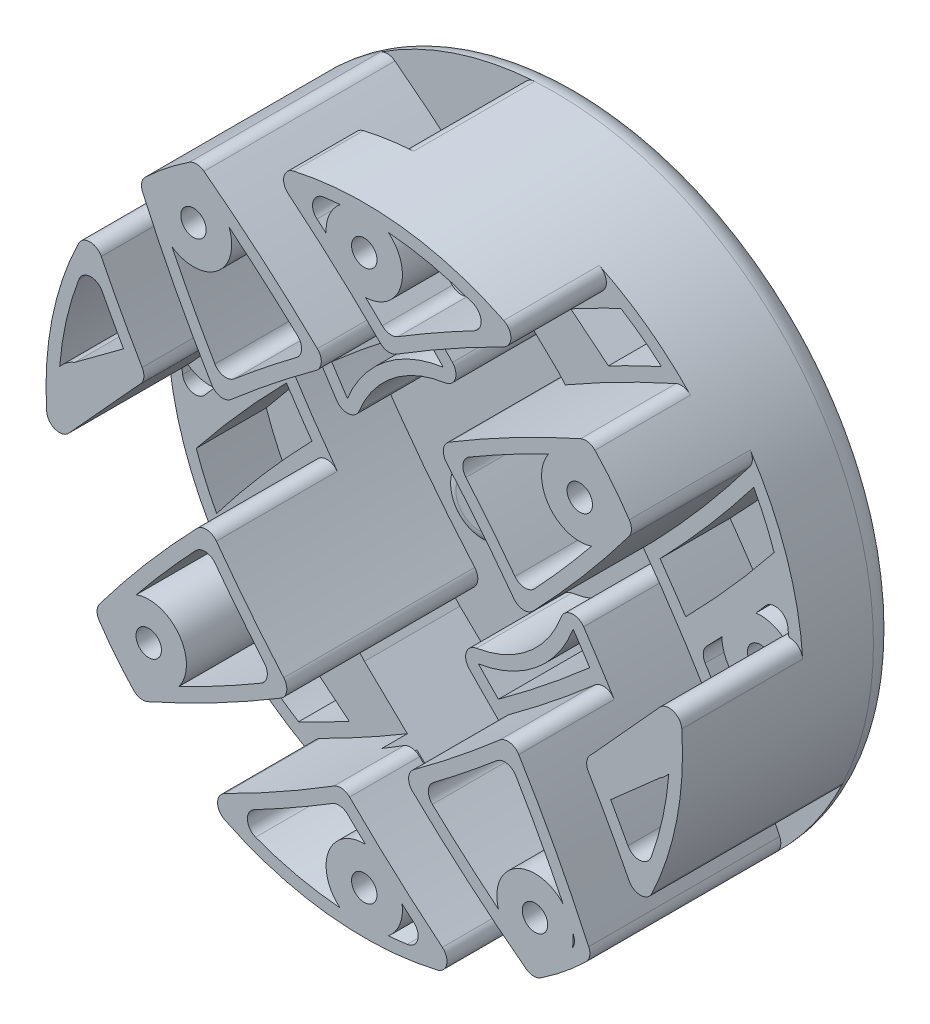
SolidWorks part; units mm, degrees
ref_plane "Front Plane" through (0, 0, 0) normal (0, 0, 1) x (1, 0, 0)
ref_plane "Top Plane" through (0, 0, 0) normal (0, 1, 0) x (1, 0, 0)
ref_plane "Right Plane" through (0, 0, 0) normal (1, 0, 0) x (0, 0, -1)
sketch "Sketch1" plane through (0, 0, 0) normal (0, 0, 1) x (1, 0, 0)
  circle A0 centre (0, 0) radius 25
extrude "Boss-Extrude1" add sketch "Sketch1" along normal blind 2
sketch "Sketch2" plane through (0, 0, 2) normal (0, 0, 1) x (1, 0, 0)
  circle A0 centre (0, 0) radius 2.8
extrude "Boss-Extrude2" add sketch "Sketch2" along normal blind 6
fillet "Fillet1" radius 1 1 edges at (2.8, 0, 8)
sketch "Sketch3" plane through (0, 0, 2) normal (0, 0, 1) x (1, 0, 0)
  line L0 (-25, 0) -> (-25, 25) construction
  line L1 (-25, 25) -> (25, 25) construction
  line L2 (25, 25) -> (25, -25) construction
  line L3 (25, -25) -> (-25, -25) construction
  line L4 (-25, -25) -> (-25, 0) construction
  line L5 (-25, 25) -> (-25, 75) construction
  line L6 (25, 25) -> (75, 25) construction
  line L7 (25, -25) -> (25, -75) construction
  line L8 (-25, -25) -> (-75, -25) construction
  line L9 (-25, 25) -> (25, -25) construction
  line L10 (25, 25) -> (-25, -25) construction
  circle A0 centre (0, 0) radius 25 construction
  circle A5 centre (0, 0) radius 13 construction
sketch "Sketch4" plane through (0, 0, 2) normal (0, 0, 1) x (1, 0, 0)
  line L0 (-25, 25) -> (-25, -9.8016) construction
  line L1 (-25, -25) -> (9.8016, -25) construction
  line L2 (25, -25) -> (25, 9.8016) construction
  line L3 (25, 25) -> (-9.8016, 25) construction
  arc A0 (28.9883, -36.3502) -> (-9.8016, 25) centre (-71.0682, -56.675) ccw construction
  arc A1 (-28.9883, 36.3502) -> (9.8016, -25) centre (71.0682, 56.675) ccw construction
  arc A2 (36.3502, 28.9883) -> (-25, -9.8016) centre (56.675, -71.0682) ccw construction
  arc A3 (-36.3502, -28.9883) -> (25, 9.8016) centre (-56.675, 71.0682) ccw construction
sketch "Sketch5" plane through (0, 0, 2) normal (0, 0, 1) x (1, 0, 0)
  line L0 (-6.2547, -4.9879) -> (0, 0) construction
  arc A0 (-6.4509, -4.7314) -> (-6.0482, -5.2363) centre (0, 0) ccw construction
sketch "Sketch6" plane through (0, 0, 2) normal (0, 0, 1) x (1, 0, 0)
  circle A0 centre (-25, 25) radius 50 construction
  circle A1 centre (25, 25) radius 50 construction
  circle A2 centre (-25, -25) radius 50 construction
  circle A3 centre (25, -25) radius 50 construction
sketch "Sketch7" plane through (0, 0, 2) normal (0, 0, 1) x (1, 0, 0)
  arc A0 (-13.1465, 21.2643) -> (-17.6984, 17.6569) centre (0, 0) ccw
  arc A1 (0.9661, 8.4449) -> (-13.1465, 21.2643) centre (-72.3464, -58.0854) ccw
  arc A3 (0.9661, 8.4449) -> (-8.4219, 1.1498) centre (0, 0) ccw
  arc A4 (-21.5033, 12.7519) -> (7.6467, -23.8018) centre (0, 0) ccw
  arc A8 (21.6702, -12.466) -> (-7.4888, 23.852) centre (-72.3464, -58.0854) ccw
  arc A9 (17.921, -17.4309) -> (8.4542, -0.8816) centre (-72.3464, -58.0854) ccw
  arc A10 (-17.6984, 17.6569) -> (-8.4219, 1.1498) centre (71.0981, 56.6976) ccw
  arc A11 (-21.5033, 12.7519) -> (7.6467, -23.8018) centre (71.0981, 56.6976) ccw
  arc A12 (13.2755, -21.184) -> (17.921, -17.4309) centre (0, 0) ccw
  arc A13 (21.6702, -12.466) -> (-7.4888, 23.852) centre (0, 0) ccw
  arc A14 (-0.7533, -8.4666) -> (8.4542, -0.8816) centre (0, 0) ccw
  arc A15 (-0.7533, -8.4666) -> (13.2755, -21.184) centre (71.0981, 56.6976) ccw
extrude "Boss-Extrude3" add sketch "Sketch7" along normal blind 7.5
sketch "Sketch8" plane through (0, 0, 9.5) normal (0, 0, 1) x (1, 0, 0)
  arc A0 (12.7137, 21.5259) -> (1.8288, 15.5237) centre (56.675, -71.0682) ccw
  arc A7 (17.6291, 17.7261) -> (5.67, 11.4394) centre (56.675, -71.0682) ccw
  arc A8 (-12.3108, -2.8775) -> (-21.2045, -13.2427) centre (56.675, -71.0682) ccw
  arc A9 (12.4368, 3.0052) -> (21.2045, 13.2427) centre (-56.675, 71.0682) ccw
  arc A10 (-17.6291, -17.7261) -> (-5.5449, -11.3619) centre (-56.675, 71.0682) ccw
  arc A11 (-12.7137, -21.5259) -> (-1.7108, -15.4488) centre (-56.675, 71.0682) ccw
  arc A15 (-17.6984, 17.6569) -> (-11.3535, 5.6024) centre (71.0981, 56.6976) ccw
  arc A16 (17.921, -17.4309) -> (11.5101, -5.4632) centre (-72.3464, -58.0854) ccw
  arc A19 (-2.8235, 12.3955) -> (-11.3535, 5.6024) centre (56.675, -71.0682) ccw
  arc A22 (-15.442, 1.77) -> (-23.8152, -7.6049) centre (56.675, -71.0682) ccw
  arc A23 (2.9354, -12.3157) -> (13.2755, -21.184) centre (71.0981, 56.6976) ccw
  arc A25 (2.9354, -12.3157) -> (11.5101, -5.4632) centre (-56.675, 71.0682) ccw
  arc A26 (-2.8235, 12.3955) -> (-13.1465, 21.2643) centre (-72.3464, -58.0854) ccw
  arc A27 (15.5881, -1.625) -> (23.8152, 7.6049) centre (-56.675, 71.0682) ccw
  arc A33 (21.6702, -12.466) -> (15.5881, -1.625) centre (-72.3464, -58.0854) ccw
  arc A35 (-21.5033, 12.7519) -> (-15.442, 1.77) centre (71.0981, 56.6976) ccw
  arc A37 (12.4368, 3.0052) -> (5.67, 11.4394) centre (-72.3464, -58.0854) ccw
  arc A38 (-1.7108, -15.4488) -> (7.6467, -23.8018) centre (71.0981, 56.6976) ccw
  arc A41 (-13.1465, 21.2643) -> (-17.6984, 17.6569) centre (0, 0) ccw
  arc A44 (1.8288, 15.5237) -> (-7.4888, 23.852) centre (-72.3464, -58.0854) ccw
  arc A45 (-12.3108, -2.8775) -> (-5.5449, -11.3619) centre (71.0981, 56.6976) ccw
  arc A48 (12.7137, 21.5259) -> (-7.4888, 23.852) centre (0, 0) ccw
  arc A50 (21.2045, 13.2427) -> (17.6291, 17.7261) centre (0, 0) ccw
  arc A52 (-21.5033, 12.7519) -> (-23.8152, -7.6049) centre (0, 0) ccw
  arc A53 (-21.2045, -13.2427) -> (-17.6291, -17.7261) centre (0, 0) ccw
  arc A54 (-12.7137, -21.5259) -> (7.6467, -23.8018) centre (0, 0) ccw
  arc A55 (13.2755, -21.184) -> (17.921, -17.4309) centre (0, 0) ccw
  arc A56 (21.6702, -12.466) -> (23.8152, 7.6049) centre (0, 0) ccw
extrude "Boss-Extrude5" add sketch "Sketch8" along normal blind 7.5
sketch "Sketch9" plane through (0, 0, 9.5) normal (0, 0, 1) x (1, 0, 0)
  arc A8 (5.8577, 12.7268) -> (3.4142, 15.3352) centre (-72.3464, -58.0854) ccw
  arc A9 (15.8486, 18.0228) -> (5.8577, 12.7268) centre (56.675, -71.0682) ccw
  arc A10 (15.8486, 18.0228) -> (12.6577, 20.3907) centre (0, 0) ccw
  arc A11 (12.6577, 20.3907) -> (3.4142, 15.3352) centre (56.675, -71.0682) ccw
  arc A12 (5.8577, 12.7268) -> (3.4142, 15.3352) centre (-72.3464, -58.0854) ccw
  arc A13 (15.8486, 18.0228) -> (5.8577, 12.7268) centre (56.675, -71.0682) ccw
  arc A14 (15.8486, 18.0228) -> (12.6577, 20.3907) centre (0, 0) ccw
  arc A15 (12.6577, 20.3907) -> (3.4142, 15.3352) centre (56.675, -71.0682) ccw
  arc A17 (10.5207, 21.5711) -> (-5.3354, 23.3994) centre (0, 0) ccw
  arc A18 (1.9721, 16.7945) -> (-5.3354, 23.3994) centre (-72.3464, -58.0854) ccw
  arc A19 (10.5207, 21.5711) -> (1.9721, 16.7945) centre (56.675, -71.0682) ccw
  arc A20 (10.5207, 21.5711) -> (-5.3354, 23.3994) centre (0, 0) ccw
  arc A21 (1.9721, 16.7945) -> (-5.3354, 23.3994) centre (-72.3464, -58.0854) ccw
  arc A22 (10.5207, 21.5711) -> (1.9721, 16.7945) centre (56.675, -71.0682) ccw
  arc A28 (12.5465, 4.552) -> (7.2083, 11.2061) centre (-72.3464, -58.0854) ccw
  arc A29 (12.5465, 4.552) -> (19.9875, 13.2853) centre (-56.675, 71.0682) ccw
  arc A30 (19.9875, 13.2853) -> (17.3998, 16.5302) centre (0, 0) ccw
  arc A31 (17.3998, 16.5302) -> (7.2083, 11.2061) centre (56.675, -71.0682) ccw
  arc A32 (12.5465, 4.552) -> (7.2083, 11.2061) centre (-72.3464, -58.0854) ccw
  arc A33 (12.5465, 4.552) -> (19.9875, 13.2853) centre (-56.675, 71.0682) ccw
  arc A34 (19.9875, 13.2853) -> (17.3998, 16.5302) centre (0, 0) ccw
  arc A35 (17.3998, 16.5302) -> (7.2083, 11.2061) centre (56.675, -71.0682) ccw
  arc A40 (15.7514, -0.0421) -> (13.737, 2.9055) centre (-72.3464, -58.0854) ccw
  arc A41 (15.7514, -0.0421) -> (22.6961, 7.803) centre (-56.675, 71.0682) ccw
  arc A42 (22.6961, 7.803) -> (21.0976, 11.4408) centre (0, 0) ccw
  arc A43 (13.737, 2.9055) -> (21.0976, 11.4408) centre (-56.675, 71.0682) ccw
  arc A44 (15.7514, -0.0421) -> (13.737, 2.9055) centre (-72.3464, -58.0854) ccw
  arc A45 (15.7514, -0.0421) -> (22.6961, 7.803) centre (-56.675, 71.0682) ccw
  arc A46 (22.6961, 7.803) -> (21.0976, 11.4408) centre (0, 0) ccw
  arc A47 (13.737, 2.9055) -> (21.0976, 11.4408) centre (-56.675, 71.0682) ccw
  arc A50 (21.6937, -10.2657) -> (23.3714, 5.4569) centre (0, 0) ccw
  arc A51 (16.8621, -1.7641) -> (23.3714, 5.4569) centre (-56.675, 71.0682) ccw
  arc A52 (21.6937, -10.2657) -> (16.8621, -1.7641) centre (-72.3464, -58.0854) ccw
  arc A53 (21.6937, -10.2657) -> (23.3714, 5.4569) centre (0, 0) ccw
  arc A54 (16.8621, -1.7641) -> (23.3714, 5.4569) centre (-56.675, 71.0682) ccw
  arc A55 (21.6937, -10.2657) -> (16.8621, -1.7641) centre (-72.3464, -58.0854) ccw
  arc A61 (-13.1932, 20.0484) -> (-16.502, 17.4265) centre (0, 0) ccw
  arc A62 (-16.502, 17.4265) -> (-11.1198, 7.1375) centre (71.0981, 56.6976) ccw
  arc A63 (-4.3737, 12.51) -> (-11.1198, 7.1375) centre (56.675, -71.0682) ccw
  arc A64 (-4.3737, 12.51) -> (-13.1932, 20.0484) centre (-72.3464, -58.0854) ccw
  arc A65 (-13.1932, 20.0484) -> (-16.502, 17.4265) centre (0, 0) ccw
  arc A66 (-16.502, 17.4265) -> (-11.1198, 7.1375) centre (71.0981, 56.6976) ccw
  arc A67 (-4.3737, 12.51) -> (-11.1198, 7.1375) centre (56.675, -71.0682) ccw
  arc A68 (-4.3737, 12.51) -> (-13.1932, 20.0484) centre (-72.3464, -58.0854) ccw
  arc A73 (-1.2957, 9.4112) -> (-2.9278, 11.0887) centre (-72.3464, -58.0854) ccw
  arc A74 (-2.9278, 11.0887) -> (-10.0552, 5.4128) centre (56.675, -71.0682) ccw
  arc A75 (-10.0552, 5.4128) -> (-8.8253, 3.5164) centre (71.0981, 56.6976) ccw
  arc A76 (-1.2957, 9.4112) -> (-8.8253, 3.5164) centre (0, 0) ccw
  arc A77 (-1.2957, 9.4112) -> (-2.9278, 11.0887) centre (-72.3464, -58.0854) ccw
  arc A78 (-2.9278, 11.0887) -> (-10.0552, 5.4128) centre (56.675, -71.0682) ccw
  arc A79 (-10.0552, 5.4128) -> (-8.8253, 3.5164) centre (71.0981, 56.6976) ccw
  arc A80 (-1.2957, 9.4112) -> (-8.8253, 3.5164) centre (0, 0) ccw
  arc A85 (1.4642, -9.3865) -> (3.0394, -11.0077) centre (71.0981, 56.6976) ccw
  arc A86 (3.0394, -11.0077) -> (10.2091, -5.2783) centre (-56.675, 71.0682) ccw
  arc A87 (10.2091, -5.2783) -> (8.9089, -3.2987) centre (-72.3464, -58.0854) ccw
  arc A88 (1.4642, -9.3865) -> (8.9089, -3.2987) centre (0, 0) ccw
  arc A89 (1.4642, -9.3865) -> (3.0394, -11.0077) centre (71.0981, 56.6976) ccw
  arc A90 (3.0394, -11.0077) -> (10.2091, -5.2783) centre (-56.675, 71.0682) ccw
  arc A91 (10.2091, -5.2783) -> (8.9089, -3.2987) centre (-72.3464, -58.0854) ccw
  arc A92 (1.4642, -9.3865) -> (8.9089, -3.2987) centre (0, 0) ccw
  arc A97 (13.3172, -19.9663) -> (16.7238, -17.2137) centre (0, 0) ccw
  arc A98 (16.7238, -17.2137) -> (11.2829, -6.9958) centre (-72.3464, -58.0854) ccw
  arc A99 (4.4839, -12.4294) -> (11.2829, -6.9958) centre (-56.675, 71.0682) ccw
  arc A100 (4.4839, -12.4294) -> (13.3172, -19.9663) centre (71.0981, 56.6976) ccw
  arc A101 (13.3172, -19.9663) -> (16.7238, -17.2137) centre (0, 0) ccw
  arc A102 (16.7238, -17.2137) -> (11.2829, -6.9958) centre (-72.3464, -58.0854) ccw
  arc A103 (4.4839, -12.4294) -> (11.2829, -6.9958) centre (-56.675, 71.0682) ccw
  arc A104 (4.4839, -12.4294) -> (13.3172, -19.9663) centre (71.0981, 56.6976) ccw
  arc A107 (-21.5507, 10.5626) -> (-23.3714, -5.4569) centre (0, 0) ccw
  arc A108 (-16.7139, 1.9135) -> (-23.3714, -5.4569) centre (56.675, -71.0682) ccw
  arc A109 (-21.5507, 10.5626) -> (-16.7139, 1.9135) centre (71.0981, 56.6976) ccw
  arc A110 (-21.5507, 10.5626) -> (-23.3714, -5.4569) centre (0, 0) ccw
  arc A111 (-16.7139, 1.9135) -> (-23.3714, -5.4569) centre (56.675, -71.0682) ccw
  arc A112 (-21.5507, 10.5626) -> (-16.7139, 1.9135) centre (71.0981, 56.6976) ccw
  arc A118 (-22.6961, -7.803) -> (-21.0976, -11.4408) centre (0, 0) ccw
  arc A119 (-13.6095, -2.774) -> (-21.0976, -11.4408) centre (56.675, -71.0682) ccw
  arc A120 (-15.6113, 0.1846) -> (-13.6095, -2.774) centre (71.0981, 56.6976) ccw
  arc A121 (-15.6113, 0.1846) -> (-22.6961, -7.803) centre (56.675, -71.0682) ccw
  arc A122 (-22.6961, -7.803) -> (-21.0976, -11.4408) centre (0, 0) ccw
  arc A123 (-13.6095, -2.774) -> (-21.0976, -11.4408) centre (56.675, -71.0682) ccw
  arc A124 (-15.6113, 0.1846) -> (-13.6095, -2.774) centre (71.0981, 56.6976) ccw
  arc A125 (-15.6113, 0.1846) -> (-22.6961, -7.803) centre (56.675, -71.0682) ccw
  arc A130 (-19.9875, -13.2853) -> (-17.3998, -16.5302) centre (0, 0) ccw
  arc A131 (-17.3998, -16.5302) -> (-7.08, -11.1288) centre (-56.675, 71.0682) ccw
  arc A132 (-12.4252, -4.4261) -> (-7.08, -11.1288) centre (71.0981, 56.6976) ccw
  arc A133 (-12.4252, -4.4261) -> (-19.9875, -13.2853) centre (56.675, -71.0682) ccw
  arc A134 (-19.9875, -13.2853) -> (-17.3998, -16.5302) centre (0, 0) ccw
  arc A135 (-17.3998, -16.5302) -> (-7.08, -11.1288) centre (-56.675, 71.0682) ccw
  arc A136 (-12.4252, -4.4261) -> (-7.08, -11.1288) centre (71.0981, 56.6976) ccw
  arc A137 (-12.4252, -4.4261) -> (-19.9875, -13.2853) centre (56.675, -71.0682) ccw
  arc A142 (-15.8486, -18.0228) -> (-12.6577, -20.3907) centre (0, 0) ccw
  arc A143 (-12.6577, -20.3907) -> (-3.2941, -15.261) centre (-56.675, 71.0682) ccw
  arc A144 (-5.7329, -12.6511) -> (-3.2941, -15.261) centre (71.0981, 56.6976) ccw
  arc A145 (-15.8486, -18.0228) -> (-5.7329, -12.6511) centre (-56.675, 71.0682) ccw
  arc A146 (-15.8486, -18.0228) -> (-12.6577, -20.3907) centre (0, 0) ccw
  arc A147 (-12.6577, -20.3907) -> (-3.2941, -15.261) centre (-56.675, 71.0682) ccw
  arc A148 (-5.7329, -12.6511) -> (-3.2941, -15.261) centre (71.0981, 56.6976) ccw
  arc A149 (-15.8486, -18.0228) -> (-5.7329, -12.6511) centre (-56.675, 71.0682) ccw
  arc A152 (-10.5207, -21.5711) -> (5.5018, -23.3609) centre (0, 0) ccw
  arc A153 (-1.8538, -16.7208) -> (5.5018, -23.3609) centre (71.0981, 56.6976) ccw
  arc A154 (-10.5207, -21.5711) -> (-1.8538, -16.7208) centre (-56.675, 71.0682) ccw
  arc A155 (-10.5207, -21.5711) -> (5.5018, -23.3609) centre (0, 0) ccw
  arc A156 (-1.8538, -16.7208) -> (5.5018, -23.3609) centre (71.0981, 56.6976) ccw
  arc A157 (-10.5207, -21.5711) -> (-1.8538, -16.7208) centre (-56.675, 71.0682) ccw
  dimension "D1" = 1
  dimension "D2" = 1
  dimension "D3" = 1
  dimension "D4" = 1
  dimension "D5" = 1
  dimension "D6" = 1
  dimension "D7" = 1
  dimension "D8" = 1
  dimension "D9" = 1
  dimension "D10" = 1
  dimension "D11" = 1
  dimension "D12" = 1
  dimension "D13" = 1
  dimension "D14" = 1
extrude "Cut-Extrude1" cut sketch "Sketch9" against normal blind 7.5 and the other way blind 7.5
fillet "Fillet2" radius 1 60 edges at (5.5018, -23.3609, 9.5) (-1.8538, -16.7208, 9.5) (-10.5207, -21.5711, 9.5) (7.6467, -23.8018, 9.5) (-12.7137, -21.5259, 13.25) (-1.7108, -15.4488, 13.25) (-17.3998, -16.5302, 9.5) (-19.9875, -13.2853, 9.5) (-12.4252, -4.4261, 9.5) (-7.08, -11.1288, 9.5) (-5.5449, -11.3619, 13.25) (-17.6291, -17.7261, 13.25) (-21.2045, -13.2427, 13.25) (-12.3108, -2.8775, 13.25) (-15.442, 1.77, 13.25) (-21.5507, 10.5626, 9.5) (-16.7139, 1.9135, 9.5) (-23.3714, -5.4569, 9.5) (-23.8152, -7.6049, 13.25) (-21.5033, 12.7519, 9.5) (-16.502, 17.4265, 9.5) (-13.1932, 20.0484, 9.5) (-17.6984, 17.6569, 9.5) (-13.1465, 21.2643, 9.5) (-11.1198, 7.1375, 9.5) (-4.3737, 12.51, 9.5) (-2.8235, 12.3955, 13.25) (-11.3535, 5.6024, 13.25) (-8.4219, 1.1498, 5.75) (0.9661, 8.4449, 5.75) (11.2829, -6.9958, 9.5) (4.4839, -12.4294, 9.5) (2.9354, -12.3157, 13.25) (11.5101, -5.4632, 13.25) (8.4542, -0.8816, 5.75) (-0.7533, -8.4666, 5.75) (13.2755, -21.184, 9.5) (13.3172, -19.9663, 9.5) (16.7238, -17.2137, 9.5) (17.921, -17.4309, 9.5) (21.6702, -12.466, 9.5) (23.8152, 7.6049, 13.25) (15.5881, -1.625, 13.25) (21.6937, -10.2657, 9.5) (23.3714, 5.4569, 9.5) (16.8621, -1.7641, 9.5) (12.4368, 3.0052, 13.25) (5.67, 11.4394, 13.25) (1.8288, 15.5237, 13.25) (21.2045, 13.2427, 13.25) (19.9875, 13.2853, 9.5) (12.5465, 4.552, 9.5) (7.2083, 11.2061, 9.5) (17.3998, 16.5302, 9.5) (17.6291, 17.7261, 13.25) (12.7137, 21.5259, 13.25) (-7.4888, 23.852, 9.5) (1.9721, 16.7945, 9.5) (10.5207, 21.5711, 9.5) (-5.3354, 23.3994, 9.5)
sketch "Sketch10" plane through (0, 0, 2) normal (0, 0, 1) x (1, 0, 0)
  line L0 (0, 0) -> (0, 50000) construction
  line L1 (0, 0) -> (50000, 0) construction
  circle A0 centre (0, 21.6011) radius 1
  circle A1 centre (0, 21.6011) radius 3
extrude "Boss-Extrude6" add sketch "Sketch10" along normal up to surface (15 mm away) up to face at (2.3897, 20.6154, 17)
pattern_circular "CirPattern1" count 4 over 360 about axis through (0, 0, 8) along (0, 0, -1) of "Boss-Extrude6"
sketch "Sketch11" plane through (0, 0, 17) normal (0, 0, 1) x (1, 0, 0)
  line L0 (0, 0) -> (50000, 0) construction
  line L1 (25, 25) -> (-25, -25) construction
  line L2 (0, 0) -> (0, 50000) construction
  point P4 (0, 0)
fillet "Fillet3" radius 2 1 edges at (25, 0, 0)
sketch "Sketch12" plane through (0, 0, 8) normal (0, 0, 1) x (1, 0, 0)
  line L0 (-14.9041, 18.8114) -> (0, 0) construction
  line L1 (0, 0) -> (39190.421, 31050.1354) construction
  circle A0 centre (0, 0) radius 21.6011 construction
  circle A1 centre (13.4143, -16.9311) radius 1
  circle A2 centre (-13.4143, 16.9311) radius 1
  circle A3 centre (-13.4143, 16.9311) radius 3
  circle A4 centre (16.9311, 13.4143) radius 1
  circle A5 centre (16.9311, 13.4143) radius 3
  circle A6 centre (-16.9311, -13.4143) radius 1
  circle A7 centre (-16.9311, -13.4143) radius 2.962
  circle A8 centre (13.4143, -16.9311) radius 3
extrude "Boss-Extrude7" add sketch "Sketch12" along normal up to surface (9 mm away) and the other way up to surface (6 mm away) up to face at (-11.3595, 14.3592, 17) other way up to face at (2.8, 0, 2)
sketch "Sketch13" plane through (0, 0, 9.5) normal (0, 0, 1) x (1, 0, 0)
  line L2 (-4.0651, 24.9442) -> (-8.3875, 24.9442)
  line L3 (-8.3875, 24.9442) -> (-6.5634, 22.5082)
  line L4 (-6.5634, 22.5082) -> (-5.9706, 22.6271)
  line L5 (6.1355, -22.5874) -> (11.1398, -23.8425)
  line L6 (11.1398, -23.8425) -> (4.2342, -24.9079)
  arc A9 (3.381, 18.2141) -> (-4.0651, 24.9442) centre (-72.3464, -58.0854) ccw
  arc A10 (1.2677, 16.0848) -> (-5.9706, 22.6271) centre (-72.3464, -58.0854) ccw
  arc A11 (1.2677, 16.0848) -> (-5.9706, 22.6271) centre (-72.3464, -58.0854) ccw
  arc A12 (8.2921, 13.0038) -> (3.381, 18.2141) centre (-72.3464, -58.0854) ccw
  arc A14 (8.7164, 12.5196) -> (3.381, 18.2141) centre (-72.3464, -58.0854) ccw construction
  arc A15 (16.9907, 17.4426) -> (6.693, 12.0631) centre (56.675, -71.0682) ccw
  arc A16 (6.4542, 10.5493) -> (1.2677, 16.0848) centre (-72.3464, -58.0854) ccw
  arc A17 (6.693, 12.0631) -> (6.4542, 10.5493) centre (7.2083, 11.2061) ccw
  arc A18 (16.9907, 17.4426) -> (6.693, 12.0631) centre (56.675, -71.0682) ccw
  arc A19 (18.1248, 17.2189) -> (16.9907, 17.4426) centre (17.3998, 16.5302) ccw
  arc A20 (18.1248, 17.2189) -> (10.9591, 22.4699) centre (0, 0) ccw
  arc A21 (10.9667, 20.6761) -> (10.9591, 22.4699) centre (10.5207, 21.5711) ccw
  arc A22 (10.9667, 20.6761) -> (2.5007, 15.9456) centre (56.675, -71.0682) ccw
  arc A23 (1.2677, 16.0848) -> (2.5007, 15.9456) centre (1.9721, 16.7945) ccw
  arc A24 (6.4542, 10.5493) -> (1.2677, 16.0848) centre (-72.3464, -58.0854) ccw
  arc A25 (6.693, 12.0631) -> (6.4542, 10.5493) centre (7.2083, 11.2061) ccw
  arc A32 (-18.1248, -17.2189) -> (-10.9591, -22.4699) centre (0, 0) ccw
  arc A33 (-10.9667, -20.6761) -> (-10.9591, -22.4699) centre (-10.5207, -21.5711) ccw
  arc A34 (-10.9667, -20.6761) -> (-2.3835, -15.8726) centre (-56.675, 71.0682) ccw
  arc A35 (-1.149, -16.0114) -> (-2.3835, -15.8726) centre (-1.8538, -16.7208) ccw
  arc A36 (-6.3247, -10.4735) -> (-1.149, -16.0114) centre (71.0981, 56.6976) ccw
  arc A37 (-6.5634, -11.985) -> (-6.3247, -10.4735) centre (-7.08, -11.1288) ccw
  arc A38 (-16.9907, -17.4426) -> (-6.5634, -11.985) centre (-56.675, 71.0682) ccw
  arc A39 (-18.1248, -17.2189) -> (-16.9907, -17.4426) centre (-17.3998, -16.5302) ccw
  arc A44 (-6.3247, -10.4735) -> (-1.149, -16.0114) centre (71.0981, 56.6976) ccw
  arc A45 (-6.5634, -11.985) -> (-6.3247, -10.4735) centre (-7.08, -11.1288) ccw
  arc A48 (8.2921, 13.0038) -> (6.693, 12.0631) centre (56.675, -71.0682) ccw
  arc A50 (-8.163, -12.9294) -> (-3.2635, -18.1395) centre (71.0981, 56.6976) ccw
  arc A51 (-1.149, -16.0114) -> (6.1355, -22.5874) centre (71.0981, 56.6976) ccw
  arc A52 (-1.149, -16.0114) -> (6.1355, -22.5874) centre (71.0981, 56.6976) ccw
  arc A53 (-3.2635, -18.1395) -> (4.2342, -24.9079) centre (71.0981, 56.6976) ccw
  arc A55 (-8.5907, -12.4395) -> (-3.2635, -18.1395) centre (71.0981, 56.6976) ccw construction
  arc A56 (-16.9907, -17.4426) -> (-6.5634, -11.985) centre (-56.675, 71.0682) ccw
  arc A57 (-8.163, -12.9294) -> (-6.5634, -11.985) centre (-56.675, 71.0682) ccw
  dimension "D1" = 0
  dimension "D2" = 0
  dimension "D3" = 0
  dimension "D4" = 3
  dimension "D5" = 0
  dimension "D6" = 0
  dimension "D7" = 3
  dimension "D8" = 0
extrude "Cut-Extrude2" cut sketch "Sketch13" against normal up to surface (7.5 mm away) up to face at (2.8, 0, 2)
sketch "Sketch15" plane through (0, 0, 17) normal (0, 0, 1) x (1, 0, 0)
  line L0 (-18.132, 3.3238) -> (-17.0584, 4.4035)
  line L1 (18.2832, -3.1715) -> (17.2176, -4.2474)
  line L2 (24.3452, 5.6843) -> (24.9182, 4.1891)
  line L3 (-24.9182, -4.1891) -> (-24.3452, -5.6843)
  arc A8 (-20.6555, 11.0083) -> (-15.8655, 2.4428) centre (71.0981, 56.6976) ccw
  arc A9 (-24.3452, -5.6843) -> (-22.598, -6.0909) centre (-23.3714, -5.4569) ccw
  arc A10 (-16.0048, 1.2084) -> (-15.8655, 2.4428) centre (-16.7139, 1.9135) ccw
  arc A11 (-16.0048, 1.2084) -> (-22.598, -6.0909) centre (56.675, -71.0682) ccw
  arc A12 (-24.3452, -5.6843) -> (-22.598, -6.0909) centre (-23.3714, -5.4569) ccw
  arc A13 (-16.0048, 1.2084) -> (-15.8655, 2.4428) centre (-16.7139, 1.9135) ccw
  arc A14 (-16.0048, 1.2084) -> (-22.598, -6.0909) centre (56.675, -71.0682) ccw
  arc A15 (-17.0584, 4.4035) -> (-15.8655, 2.4428) centre (71.0981, 56.6976) ccw
  arc A25 (-18.132, 3.3238) -> (-24.9182, -4.1891) centre (56.675, -71.0682) ccw
  arc A26 (18.2832, -3.1715) -> (24.9182, 4.1891) centre (-56.675, 71.0682) ccw
  arc A29 (24.3452, 5.6843) -> (22.598, 6.0909) centre (23.3714, 5.4569) ccw
  arc A30 (16.1516, -1.0604) -> (22.598, 6.0909) centre (-56.675, 71.0682) ccw
  arc A31 (16.1516, -1.0604) -> (16.0166, -2.298) centre (16.8621, -1.7641) ccw
  arc A32 (20.8023, -10.719) -> (16.0166, -2.298) centre (-72.3464, -58.0854) ccw
  arc A33 (24.3452, 5.6843) -> (22.598, 6.0909) centre (23.3714, 5.4569) ccw
  arc A34 (16.1516, -1.0604) -> (22.598, 6.0909) centre (-56.675, 71.0682) ccw
  arc A35 (16.1516, -1.0604) -> (16.0166, -2.298) centre (16.8621, -1.7641) ccw
  arc A36 (17.2176, -4.2474) -> (16.0166, -2.298) centre (-72.3464, -58.0854) ccw
  dimension "D1" = 0
  dimension "D2" = 0
  dimension "D3" = 0
  dimension "D4" = 3
extrude "Cut-Extrude3" cut sketch "Sketch15" against normal up to surface (7.5 mm away) up to face at (-18.2376, -5.3028, 9.5)
sketch "Sketch16" plane through (0, 0, 17) normal (0, 0, 1) x (1, 0, 0)
  line L0 (-17.0584, 4.4035) -> (-17.7864, 3.6714)
  line L1 (-17.7864, 3.6714) -> (-24.6917, -3.9138)
  line L2 (24.6917, 3.9138) -> (17.9435, -3.5145)
  line L3 (17.9435, -3.5145) -> (17.2176, -4.2474)
  line L4 (-24.6917, -3.9138) -> (-23.9249, 1.8973)
  line L5 (-23.9249, 1.8973) -> (-18.9114, 5.6042)
  line L6 (-18.9114, 5.6042) -> (-17.0584, 4.4035)
  line L7 (24.6917, 3.9138) -> (23.9249, -1.8973)
  line L8 (23.9249, -1.8973) -> (19.3608, -5.9314)
  line L9 (19.3608, -5.9314) -> (17.2176, -4.2474)
  arc A0 (-20.5934, 8.6882) -> (-17.1256, 2.5791) centre (71.0981, 56.6976) ccw construction
  arc A1 (20.7135, -8.3852) -> (17.9435, -3.5145) centre (-72.3464, -58.0854) ccw construction
extrude "Boss-Extrude8" add sketch "Sketch16" against normal up to surface (15 mm away) up to face at (19.9796, -4.1029, 2)
sketch "Sketch17" plane through (0, 0, 2) normal (0, 0, 1) x (1, 0, 0)
  line L0 (-3.7837, 24.712) -> (7.7243, 13.6428)
  line L1 (7.7243, 13.6428) -> (8.2921, 13.0038)
  line L2 (3.9619, -24.6841) -> (-7.4858, -13.6928)
  line L3 (-7.4858, -13.6928) -> (-8.163, -12.9294)
  line L4 (-3.7837, 24.712) -> (1.8973, 23.9249)
  line L5 (1.8973, 23.9249) -> (11.6805, 15.9922)
  line L6 (11.6805, 15.9922) -> (8.2921, 13.0038)
  line L7 (3.9619, -24.6841) -> (-1.8973, -23.9249)
  line L8 (-1.8973, -23.9249) -> (-11.6151, -15.9583)
  line L9 (-11.6151, -15.9583) -> (-8.163, -12.9294)
  arc A0 (8.2921, 13.0038) -> (7.6132, 13.7666) centre (-72.3464, -58.0854) ccw construction
  arc A1 (15.8486, 18.0228) -> (7.6132, 13.7666) centre (56.675, -71.0682) ccw construction
  arc A2 (-15.8486, -18.0228) -> (-7.4858, -13.6928) centre (-56.675, 71.0682) ccw construction
extrude "Boss-Extrude9" add sketch "Sketch17" along normal up to surface (7.5 mm away) up to face at (-11.1272, -17.7153, 9.5)
fillet "Fillet4" radius 1 6 edges at (3.9619, -24.6841, 5.75) (-3.7837, 24.712, 5.75) (-17.0584, 4.4035, 13.25) (-24.6917, -3.9138, 13.25) (17.2176, -4.2474, 13.25) (24.6917, 3.9138, 13.25)
sketch "Sketch18" plane through (0, 0, 9.5) normal (0, 0, -1) x (-1, 0, 0)
  line L6 (-3.4862, 17.7193) -> (-4.2333, 17.0007)
  line L7 (2.2422, 23.2292) -> (0.9304, 21.9675)
  line L8 (-0.4023, 20.6856) -> (-1.8806, 19.2637)
  line L9 (-3.4862, 17.7193) -> (-4.2333, 17.0007)
  line L10 (2.2422, 23.2292) -> (0.9304, 21.9675)
  line L11 (-0.4023, 20.6856) -> (-1.8806, 19.2637)
  arc A32 (-2.5007, 15.9456) -> (-4.2333, 17.0007) centre (-56.675, -71.0682) ccw
  arc A33 (-2.5007, 15.9456) -> (-1.2677, 16.0848) centre (-1.9721, 16.7945) ccw
  arc A34 (5.9706, 22.6271) -> (-1.2677, 16.0848) centre (72.3464, -58.0854) ccw
  arc A35 (5.9706, 22.6271) -> (5.5577, 24.3744) centre (5.3354, 23.3994) ccw
  arc A36 (5.5577, 24.3744) -> (1.6135, 24.9479) centre (0, 0) ccw
  arc A37 (2.5453, 23.8646) -> (1.6135, 24.9479) centre (1.549, 23.95) ccw
  arc A38 (3.1936, 23.7866) -> (2.5453, 23.8646) centre (0, 0) ccw
  arc A39 (3.7111, 22.036) -> (3.1936, 23.7866) centre (3.0605, 22.7955) ccw
  arc A40 (3.7111, 22.036) -> (2.9943, 21.4164) centre (72.3464, -58.0854) ccw
  arc A41 (2.9943, 21.4164) -> (2.3919, 23.4119) centre (0, 21.6011) ccw
  arc A42 (2.2422, 23.2292) -> (2.3919, 23.4119) centre (1.549, 23.95) ccw
  arc A43 (-0.4023, 20.6856) -> (0.9304, 21.9675) centre (0, 21.6011) ccw
  arc A44 (-1.8806, 19.2637) -> (-0.1047, 18.6029) centre (0, 21.6011) ccw
  arc A45 (-0.1047, 18.6029) -> (-1.4156, 17.3428) centre (72.3464, -58.0854) ccw
  arc A46 (-2.6369, 17.2049) -> (-1.4156, 17.3428) centre (-2.1148, 18.0578) ccw
  arc A47 (-2.6369, 17.2049) -> (-3.4862, 17.7193) centre (-56.675, -71.0682) ccw
  arc A48 (-2.5007, 15.9456) -> (-4.2333, 17.0007) centre (-56.675, -71.0682) ccw
  arc A49 (-2.5007, 15.9456) -> (-1.2677, 16.0848) centre (-1.9721, 16.7945) ccw
  arc A50 (5.9706, 22.6271) -> (-1.2677, 16.0848) centre (72.3464, -58.0854) ccw
  arc A51 (5.9706, 22.6271) -> (5.5577, 24.3744) centre (5.3354, 23.3994) ccw
  arc A52 (5.5577, 24.3744) -> (1.6135, 24.9479) centre (0, 0) ccw
  arc A53 (2.5453, 23.8646) -> (1.6135, 24.9479) centre (1.549, 23.95) ccw
  arc A54 (3.1936, 23.7866) -> (2.5453, 23.8646) centre (0, 0) ccw
  arc A55 (3.7111, 22.036) -> (3.1936, 23.7866) centre (3.0605, 22.7955) ccw
  arc A56 (3.7111, 22.036) -> (2.9943, 21.4164) centre (72.3464, -58.0854) ccw
  arc A57 (2.9943, 21.4164) -> (2.3919, 23.4119) centre (0, 21.6011) ccw
  arc A58 (2.2422, 23.2292) -> (2.3919, 23.4119) centre (1.549, 23.95) ccw
  arc A59 (-0.4023, 20.6856) -> (0.9304, 21.9675) centre (0, 21.6011) ccw
  arc A60 (-1.8806, 19.2637) -> (-0.1047, 18.6029) centre (0, 21.6011) ccw
  arc A61 (-0.1047, 18.6029) -> (-1.4156, 17.3428) centre (72.3464, -58.0854) ccw
  arc A62 (-2.6369, 17.2049) -> (-1.4156, 17.3428) centre (-2.1148, 18.0578) ccw
  arc A63 (-2.6369, 17.2049) -> (-3.4862, 17.7193) centre (-56.675, -71.0682) ccw
  dimension "D1" = 0
extrude "Cut-Extrude4" cut sketch "Sketch18" against normal blind 2
sketch "Sketch19" plane through (0, 0, 9.5) normal (0, 0, -1) x (-1, 0, 0)
  line L6 (3.3668, -17.6476) -> (4.1144, -16.9298)
  line L7 (-2.4324, -23.2155) -> (-0.9763, -21.8175)
  line L8 (0.2559, -20.6344) -> (1.7711, -19.1796)
  line L9 (3.3668, -17.6476) -> (4.1144, -16.9298)
  line L10 (-2.4324, -23.2155) -> (-0.9763, -21.8175)
  line L11 (0.2559, -20.6344) -> (1.7711, -19.1796)
  arc A32 (2.3835, -15.8726) -> (4.1144, -16.9298) centre (56.675, 71.0682) ccw
  arc A33 (2.3835, -15.8726) -> (1.149, -16.0114) centre (1.8538, -16.7208) ccw
  arc A34 (-6.1355, -22.5874) -> (1.149, -16.0114) centre (-71.0981, 56.6976) ccw
  arc A35 (-6.1355, -22.5874) -> (-5.731, -24.3342) centre (-5.5018, -23.3609) ccw
  arc A36 (-5.731, -24.3342) -> (-1.8123, -24.9342) centre (0, 0) ccw
  arc A37 (-2.7355, -23.8436) -> (-1.8123, -24.9342) centre (-1.7398, -23.9369) ccw
  arc A38 (-3.3788, -23.761) -> (-2.7355, -23.8436) centre (0, 0) ccw
  arc A39 (-3.8874, -22.0105) -> (-3.3788, -23.761) centre (-3.238, -22.7709) ccw
  arc A40 (-3.8874, -22.0105) -> (-2.9761, -21.2231) centre (-71.0981, 56.6976) ccw
  arc A41 (-2.9761, -21.2231) -> (-2.4895, -23.2751) centre (0, -21.6011) ccw
  arc A42 (-2.4324, -23.2155) -> (-2.4895, -23.2751) centre (-1.7398, -23.9369) ccw
  arc A43 (0.2559, -20.6344) -> (-0.9763, -21.8175) centre (0, -21.6011) ccw
  arc A44 (1.7711, -19.1796) -> (-0.09, -18.6024) centre (0, -21.6011) ccw
  arc A45 (-0.09, -18.6024) -> (1.2965, -17.2703) centre (-71.0981, 56.6976) ccw
  arc A46 (2.5193, -17.1328) -> (1.2965, -17.2703) centre (1.996, -17.985) ccw
  arc A47 (2.5193, -17.1328) -> (3.3668, -17.6476) centre (56.675, 71.0682) ccw
  arc A48 (2.3835, -15.8726) -> (4.1144, -16.9298) centre (56.675, 71.0682) ccw
  arc A49 (2.3835, -15.8726) -> (1.149, -16.0114) centre (1.8538, -16.7208) ccw
  arc A50 (-6.1355, -22.5874) -> (1.149, -16.0114) centre (-71.0981, 56.6976) ccw
  arc A51 (-6.1355, -22.5874) -> (-5.731, -24.3342) centre (-5.5018, -23.3609) ccw
  arc A52 (-5.731, -24.3342) -> (-1.8123, -24.9342) centre (0, 0) ccw
  arc A53 (-2.7355, -23.8436) -> (-1.8123, -24.9342) centre (-1.7398, -23.9369) ccw
  arc A54 (-3.3788, -23.761) -> (-2.7355, -23.8436) centre (0, 0) ccw
  arc A55 (-3.8874, -22.0105) -> (-3.3788, -23.761) centre (-3.238, -22.7709) ccw
  arc A56 (-3.8874, -22.0105) -> (-2.9761, -21.2231) centre (-71.0981, 56.6976) ccw
  arc A57 (-2.9761, -21.2231) -> (-2.4895, -23.2751) centre (0, -21.6011) ccw
  arc A58 (-2.4324, -23.2155) -> (-2.4895, -23.2751) centre (-1.7398, -23.9369) ccw
  arc A59 (0.2559, -20.6344) -> (-0.9763, -21.8175) centre (0, -21.6011) ccw
  arc A60 (1.7711, -19.1796) -> (-0.09, -18.6024) centre (0, -21.6011) ccw
  arc A61 (-0.09, -18.6024) -> (1.2965, -17.2703) centre (-71.0981, 56.6976) ccw
  arc A62 (2.5193, -17.1328) -> (1.2965, -17.2703) centre (1.996, -17.985) ccw
  arc A63 (2.5193, -17.1328) -> (3.3668, -17.6476) centre (56.675, 71.0682) ccw
  dimension "D1" = 0
extrude "Cut-Extrude5" cut sketch "Sketch19" against normal blind 2
sketch "Sketch20" plane through (0, 0, 9.5) normal (0, 0, 1) x (1, 0, 0)
  line L6 (-17.6024, 3.8564) -> (-17.7864, 3.6714)
  line L7 (-19.3369, 1.9682) -> (-20.712, 0.4578)
  line L8 (-21.9736, -0.928) -> (-23.2065, -2.2824)
  line L9 (-17.6024, 3.8564) -> (-17.7864, 3.6714)
  line L10 (-19.3369, 1.9682) -> (-20.712, 0.4578)
  line L11 (-21.9736, -0.928) -> (-23.2065, -2.2824)
  arc A34 (-23.8582, -2.6053) -> (-23.7681, -3.3282) centre (0, 0) ccw
  arc A35 (-24.9437, -1.6762) -> (-23.8582, -2.6053) centre (-23.946, -1.6092) ccw
  arc A36 (-24.9437, -1.6762) -> (-20.8203, -13.8388) centre (0, 0) ccw
  arc A37 (-20.7861, -12.6834) -> (-20.8203, -13.8388) centre (-19.9875, -13.2853) ccw
  arc A38 (-13.145, -3.7319) -> (-20.7861, -12.6834) centre (56.675, -71.0682) ccw
  arc A39 (-11.6182, -3.8355) -> (-13.145, -3.7319) centre (-12.4252, -4.4261) ccw
  arc A40 (-17.4476, 5.0653) -> (-11.6182, -3.8355) centre (71.0981, 56.6976) ccw
  arc A41 (-17.6024, 3.8564) -> (-17.4476, 5.0653) centre (-18.3115, 4.5615) ccw
  arc A42 (-17.7864, 3.6714) -> (-17.1256, 2.5791) centre (71.0981, 56.6976) ccw
  arc A43 (-17.2637, 1.3565) -> (-17.1256, 2.5791) centre (-17.978, 2.0562) ccw
  arc A44 (-17.2637, 1.3565) -> (-18.6013, -0.0348) centre (56.675, -71.0682) ccw
  arc A45 (-18.6013, -0.0348) -> (-19.3369, 1.9682) centre (-21.6011, 0) ccw
  arc A46 (-21.9736, -0.928) -> (-20.712, 0.4578) centre (-21.6011, 0) ccw
  arc A47 (-23.3675, -2.4248) -> (-23.2065, -2.2824) centre (-23.946, -1.6092) ccw
  arc A48 (-23.3675, -2.4248) -> (-21.2775, -2.9825) centre (-21.6011, 0) ccw
  arc A49 (-21.2775, -2.9825) -> (-22.0175, -3.8391) centre (56.675, -71.0682) ccw
  arc A50 (-23.7681, -3.3282) -> (-22.0175, -3.8391) centre (-22.7778, -3.1895) ccw
  arc A51 (-23.8582, -2.6053) -> (-23.7681, -3.3282) centre (0, 0) ccw
  arc A52 (-24.9437, -1.6762) -> (-23.8582, -2.6053) centre (-23.946, -1.6092) ccw
  arc A53 (-24.9437, -1.6762) -> (-20.8203, -13.8388) centre (0, 0) ccw
  arc A54 (-20.7861, -12.6834) -> (-20.8203, -13.8388) centre (-19.9875, -13.2853) ccw
  arc A55 (-13.145, -3.7319) -> (-20.7861, -12.6834) centre (56.675, -71.0682) ccw
  arc A56 (-11.6182, -3.8355) -> (-13.145, -3.7319) centre (-12.4252, -4.4261) ccw
  arc A57 (-17.4476, 5.0653) -> (-11.6182, -3.8355) centre (71.0981, 56.6976) ccw
  arc A58 (-17.6024, 3.8564) -> (-17.4476, 5.0653) centre (-18.3115, 4.5615) ccw
  arc A59 (-17.7864, 3.6714) -> (-17.1256, 2.5791) centre (71.0981, 56.6976) ccw
  arc A60 (-17.2637, 1.3565) -> (-17.1256, 2.5791) centre (-17.978, 2.0562) ccw
  arc A61 (-17.2637, 1.3565) -> (-18.6013, -0.0348) centre (56.675, -71.0682) ccw
  arc A62 (-18.6013, -0.0348) -> (-19.3369, 1.9682) centre (-21.6011, 0) ccw
  arc A63 (-21.9736, -0.928) -> (-20.712, 0.4578) centre (-21.6011, 0) ccw
  arc A64 (-23.3675, -2.4248) -> (-23.2065, -2.2824) centre (-23.946, -1.6092) ccw
  arc A65 (-23.3675, -2.4248) -> (-21.2775, -2.9825) centre (-21.6011, 0) ccw
  arc A66 (-21.2775, -2.9825) -> (-22.0175, -3.8391) centre (56.675, -71.0682) ccw
  arc A67 (-23.7681, -3.3282) -> (-22.0175, -3.8391) centre (-22.7778, -3.1895) ccw
  dimension "D1" = 0
extrude "Cut-Extrude6" cut sketch "Sketch20" against normal blind 2
sketch "Sketch21" plane through (0, 0, 9.5) normal (0, 0, 1) x (1, 0, 0)
  line L6 (17.7627, -3.697) -> (17.9435, -3.5145)
  line L7 (19.3425, -1.9745) -> (20.715, -0.4636)
  line L8 (21.9778, 0.9263) -> (23.206, 2.2784)
  line L9 (17.7627, -3.697) -> (17.9435, -3.5145)
  line L10 (19.3425, -1.9745) -> (20.715, -0.4636)
  line L11 (21.9778, 0.9263) -> (23.206, 2.2784)
  arc A34 (23.8585, 2.6021) -> (23.7681, 3.3282) centre (0, 0) ccw
  arc A35 (24.944, 1.6729) -> (23.8585, 2.6021) centre (23.9462, 1.606) ccw
  arc A36 (24.944, 1.6729) -> (20.8203, 13.8388) centre (0, 0) ccw
  arc A37 (20.7861, 12.6834) -> (20.8203, 13.8388) centre (19.9875, 13.2853) ccw
  arc A38 (13.2675, 3.8592) -> (20.7861, 12.6834) centre (-56.675, 71.0682) ccw
  arc A39 (11.7418, 3.9583) -> (13.2675, 3.8592) centre (12.5465, 4.552) ccw
  arc A40 (17.6124, -4.9096) -> (11.7418, 3.9583) centre (-72.3464, -58.0854) ccw
  arc A41 (17.7627, -3.697) -> (17.6124, -4.9096) centre (18.4732, -4.4007) ccw
  arc A42 (17.9435, -3.5145) -> (17.279, -2.4299) centre (-72.3464, -58.0854) ccw
  arc A43 (17.4127, -1.204) -> (17.279, -2.4299) centre (18.1285, -1.9023) ccw
  arc A44 (17.4127, -1.204) -> (18.6013, 0.0348) centre (-56.675, 71.0682) ccw
  arc A45 (18.6013, 0.0348) -> (19.3425, -1.9745) centre (21.6011, 0) ccw
  arc A46 (21.9778, 0.9263) -> (20.715, -0.4636) centre (21.6011, 0) ccw
  arc A47 (23.3698, 2.4231) -> (23.206, 2.2784) centre (23.9462, 1.606) ccw
  arc A48 (23.3698, 2.4231) -> (21.2775, 2.9825) centre (21.6011, 0) ccw
  arc A49 (21.2775, 2.9825) -> (22.0175, 3.8391) centre (-56.675, 71.0682) ccw
  arc A50 (23.7681, 3.3282) -> (22.0175, 3.8391) centre (22.7778, 3.1895) ccw
  arc A51 (23.8585, 2.6021) -> (23.7681, 3.3282) centre (0, 0) ccw
  arc A52 (24.944, 1.6729) -> (23.8585, 2.6021) centre (23.9462, 1.606) ccw
  arc A53 (24.944, 1.6729) -> (20.8203, 13.8388) centre (0, 0) ccw
  arc A54 (20.7861, 12.6834) -> (20.8203, 13.8388) centre (19.9875, 13.2853) ccw
  arc A55 (13.2675, 3.8592) -> (20.7861, 12.6834) centre (-56.675, 71.0682) ccw
  arc A56 (11.7418, 3.9583) -> (13.2675, 3.8592) centre (12.5465, 4.552) ccw
  arc A57 (17.6124, -4.9096) -> (11.7418, 3.9583) centre (-72.3464, -58.0854) ccw
  arc A58 (17.7627, -3.697) -> (17.6124, -4.9096) centre (18.4732, -4.4007) ccw
  arc A59 (17.9435, -3.5145) -> (17.279, -2.4299) centre (-72.3464, -58.0854) ccw
  arc A60 (17.4127, -1.204) -> (17.279, -2.4299) centre (18.1285, -1.9023) ccw
  arc A61 (17.4127, -1.204) -> (18.6013, 0.0348) centre (-56.675, 71.0682) ccw
  arc A62 (18.6013, 0.0348) -> (19.3425, -1.9745) centre (21.6011, 0) ccw
  arc A63 (21.9778, 0.9263) -> (20.715, -0.4636) centre (21.6011, 0) ccw
  arc A64 (23.3698, 2.4231) -> (23.206, 2.2784) centre (23.9462, 1.606) ccw
  arc A65 (23.3698, 2.4231) -> (21.2775, 2.9825) centre (21.6011, 0) ccw
  arc A66 (21.2775, 2.9825) -> (22.0175, 3.8391) centre (-56.675, 71.0682) ccw
  arc A67 (23.7681, 3.3282) -> (22.0175, 3.8391) centre (22.7778, 3.1895) ccw
  dimension "D1" = 0
extrude "Cut-Extrude7" cut sketch "Sketch21" against normal blind 2
